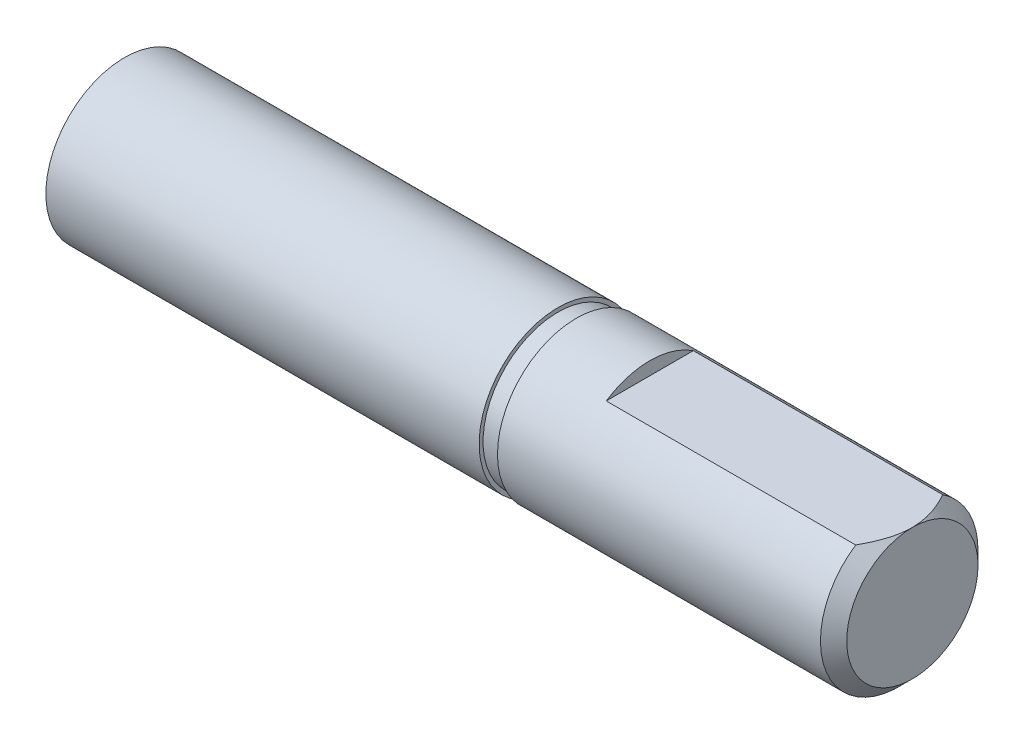
SolidWorks part; units mm, degrees
material "Chrome Stainless Steel"
ref_plane "Front Plane" through (0, 0, 0) normal (0, 0, 1) x (1, 0, 0)
ref_plane "Top Plane" through (0, 0, 0) normal (0, 1, 0) x (1, 0, 0)
ref_plane "Right Plane" through (0, 0, 0) normal (1, 0, 0) x (0, 0, -1)
sketch "BodyS" plane through (0, 0, 0) normal (1, 0, 0) x (0, 0, -1)
  circle A0 centre (0, 0) radius 3
  dimension "Dia" = 6
extrude "Body" add sketch "BodyS" against normal mid plane 30
ref_plane "FlatP" through (0, 3, 0) normal (0, 1, 0) x (1, 0, 0)
sketch "FlatS" plane through (0, 3, 0) normal (0, 1, 0) x (1, 0, 0)
  line L0 (15, -3) -> (15, 3) construction
  line L1 (5, 3) -> (15, 3)
  line L2 (5, 3) -> (5, -3)
  line L3 (5, -3) -> (15, -3)
  line L4 (15, 3) -> (15, -3)
  line L5 (5, 3) -> (15, -3) construction
  line L6 (5, -3) -> (15, 3) construction
  point P0 (10, 0)
  point P9 (15, 0)
  dimension "Length" = 10
extrude "Flat" cut sketch "FlatS" against normal blind 0.5
ref_plane "Plane1" through (-15, 0, 0) normal (0, -1, 0) x (0, 0, -1)
sketch "GrooveS" plane through (-15, 0, 0) normal (0, -1, 0) x (0, 0, -1)
  line L0 (2.85, 16.5) -> (3.6, 16.5)
  line L1 (3.6, 16.5) -> (3.6, 17.2)
  line L2 (3.6, 17.2) -> (2.85, 17.2)
  line L3 (2.85, 17.2) -> (2.85, 16.5)
  line L4 (0, -47.5) -> (0, 52.5) construction
  line L5 (3, 30) -> (-3, 30) construction
  line L6 (3, 0) -> (3, 30) construction
  dimension "Height" = 13.5
  dimension "GrooveDia" = 5.7
  dimension "Width" = 0.7
  dimension "GrooveDepth" = 0.15
  dimension "Length" = 0.75
revolve "Groove for ANSI B27.7 - 3AM1-6, Basic External Retaining Ring1" cut sketch "GrooveS"
chamfer "Chamfer1" distance 0.5 angle 45 1 edges at (15, -3, 0)
